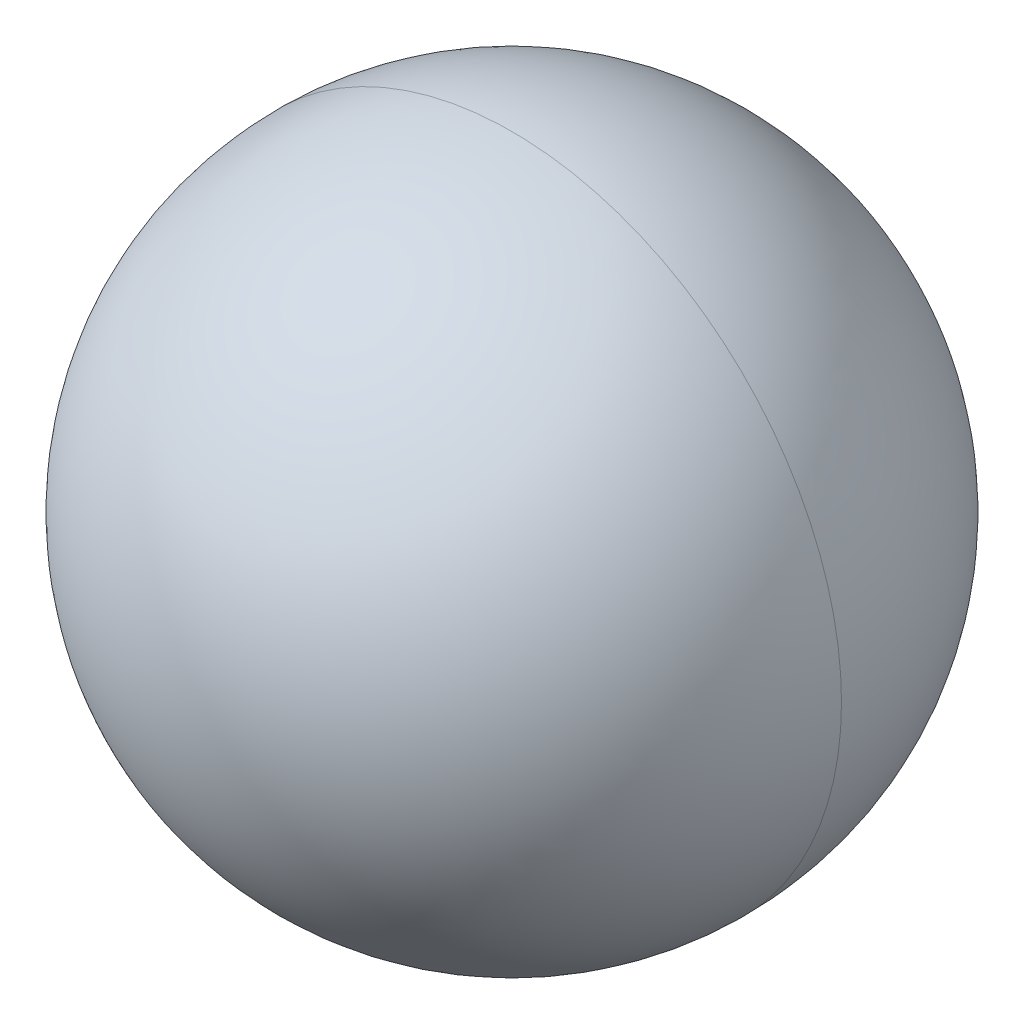
SolidWorks part; units mm, degrees
ref_plane "前视基准面" through (0, 0, 0) normal (0, 0, 1) x (1, 0, 0)
ref_plane "上视基准面" through (0, 0, 0) normal (0, 1, 0) x (1, 0, 0)
ref_plane "右视基准面" through (0, 0, 0) normal (1, 0, 0) x (0, 0, -1)
sketch "草图1" plane through (0, 0, 0) normal (0, 0, 1) x (1, 0, 0)
  circle A0 centre (0, 0) radius 1.5
  dimension "D1" = 3
extrude "凸台-拉伸1" add sketch "草图1" along normal blind 3
fillet "圆角1" radius 1.5 2 edges at (1.5, 0, 0) (1.5, 0, 3)
